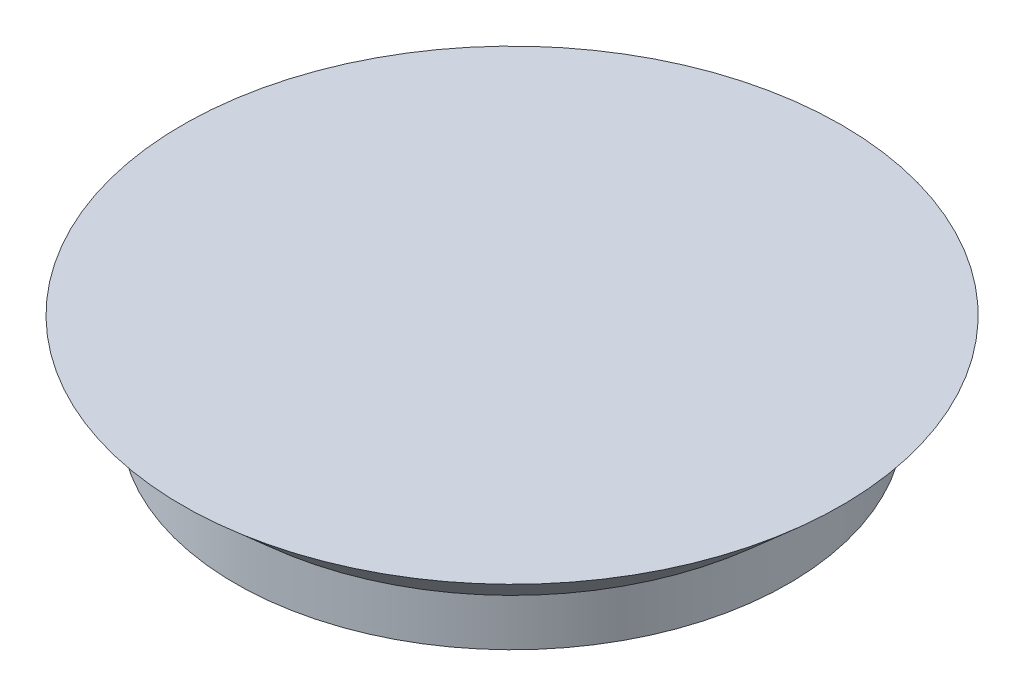
SolidWorks part; units mm, degrees
ref_plane "Front Plane" through (0, 0, 0) normal (0, 0, 1) x (1, 0, 0)
ref_plane "Top Plane" through (0, 0, 0) normal (0, 1, 0) x (1, 0, 0)
ref_plane "Right Plane" through (0, 0, 0) normal (1, 0, 0) x (0, 0, -1)
sketch "Sketch1" plane through (0, 0, 0) normal (1, 0, 0) x (0, 0, -1)
  line L0 (-11.75, 0) -> (-14, 0) construction
  line L1 (-14, 0) -> (-14, 2) construction
  line L2 (-14, 2) -> (0, 2)
  line L3 (0, 2) -> (0, 0)
  line L4 (-11.75, 0) -> (-11.75, -2)
  line L5 (-11.75, -2) -> (-2.5, -2)
  line L7 (-2.5, -7) -> (-1.5, -7)
  line L8 (0, -2) -> (0, 0)
  line L9 (-2.5, -7) -> (-2.5, -2)
  line L10 (-1.5, -7) -> (-1.5, -2)
  line L11 (-1.5, -2) -> (0, -2)
  line L12 (-11.75, 0) -> (-14, 2)
  point P8 (-0.75, -2)
  dimension "D1" = 2
  dimension "D2" = 2.25
  dimension "D3" = 2
  dimension "D4" = 1
  dimension "D5" = 14
  dimension "D6" = 9
  dimension "D7" = 1.5
  dimension "D8" = 2.5
revolve "Revolve1" add sketch "Sketch1" angle 360 about L8
